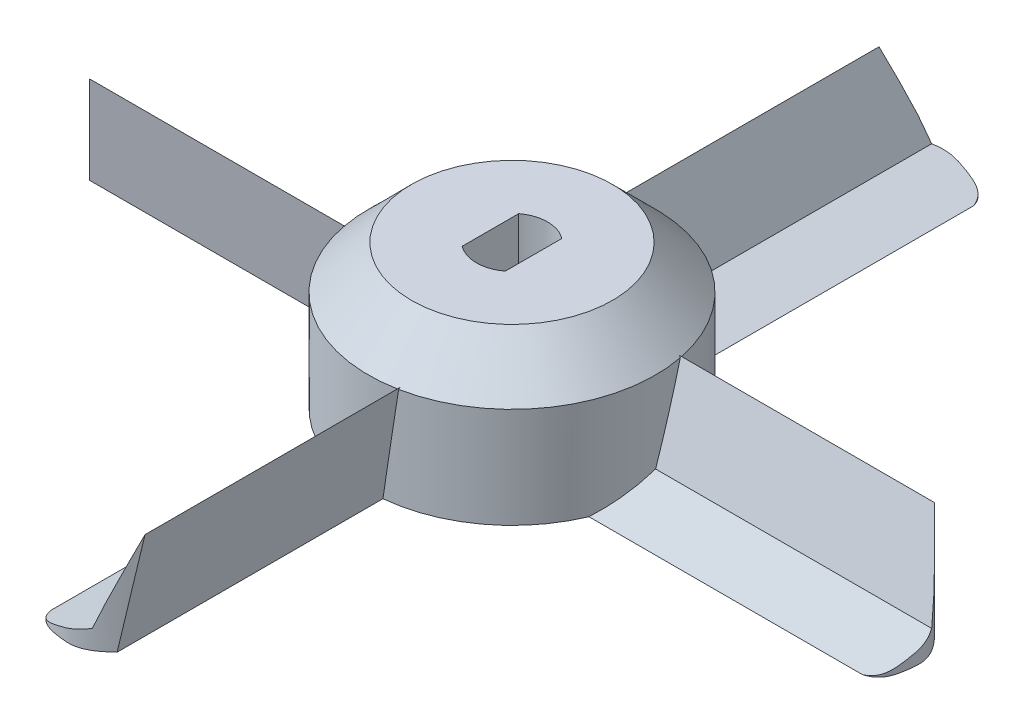
SolidWorks part; units mm, degrees
ref_plane "Front Plane" through (0, 0, 0) normal (0, 0, 1) x (1, 0, 0)
ref_plane "Top Plane" through (0, 0, 0) normal (0, 1, 0) x (1, 0, 0)
ref_plane "Right Plane" through (0, 0, 0) normal (1, 0, 0) x (0, 0, -1)
sketch "Sketch1" plane through (0, 0, 0) normal (0, 1, 0) x (1, 0, 0)
  circle A0 centre (0, 0) radius 10
  dimension "D1" = 20
extrude "Boss-Extrude2" add sketch "Sketch1" along normal blind 10
ref_plane "Plane2" through (0, 0, 8) normal (0, 0, 1) x (1, 0, 0)
ref_plane "Plane3" through (0, 0, 30) normal (0, 0, 1) x (1, 0, 0)
sketch "Sketch2" plane through (0, 0, 8) normal (0, 0, 1) x (1, 0, 0)
  line L0 (0, 11.9193) -> (0, -3.7581) construction
  line L1 (0, 1.3341) -> (1.9332, 7.0864)
  line L2 (1.9332, 7.0864) -> (0.9666, 0)
  line L3 (-10, 0) -> (10, 0) construction
  line L4 (0.9666, 0) -> (-3.8663, 0)
  line L5 (-3.8663, 0) -> (0, 1.3341)
sketch "Sketch3" plane through (0, 0, 30) normal (0, 0, 1) x (1, 0, 0)
  line L0 (0, 1.3341) -> (1.9332, 7.0864)
  line L1 (1.9332, 7.0864) -> (0.9666, 0)
  line L2 (0.9666, 0) -> (-3.8663, 0)
  line L3 (-3.8663, 0) -> (0, 1.3341)
loft "Loft1" add profiles "Sketch2", "Sketch3" connector at (1.9332, 7.0864, 8) connector at (1.9332, 7.0864, 30)
ref_axis "Axis1" through (0, 10, 0) along (0, -1, 0)
pattern_circular "CirPattern1" count 4 over 360 about axis through (0, 10, 0) along (0, -1, 0) of "Loft1"
sketch "Sketch8" plane through (0, 10, 0) normal (0, 1, 0) x (1, 0, 0)
  line L0 (1.5, 1.9687) -> (1.5, -1.9687)
  line L17 (-1.5, 1.9687) -> (-1.5, -1.9687)
  arc A2 (1.5, 1.9687) -> (-1.5, 1.9687) centre (0, 0) ccw
  arc A3 (-1.5, -1.9687) -> (1.5, -1.9687) centre (0, 0) ccw
  point P6 (0, 0)
  point P14 (-1.491, 1.9755)
  dimension "D1" = 4.95
extrude "Cut-Extrude3" cut sketch "Sketch8" against normal blind 6.15 contours L0 A3 L17 A2
sketch "Sketch9" plane through (0, 0, 0) normal (0, -1, 0) x (1, 0, 0)
  line L0 (9.2223, 3.8663) -> (30, 3.8663) construction
  line L1 (9.9532, -0.9666) -> (30, -0.9666) construction
  line L3 (28.2747, 3.8663) -> (30.0234, 3.8663)
  line L4 (30.0234, 3.8663) -> (30.0234, -1.9332)
  line L5 (30.0234, -1.9332) -> (27.4896, -1.9332)
  spline S0 degree 3 poles (28.2747, 3.8663) (29.2516, 3.5799) (29.5037, 2.4698) (29.7813, 0.0895) (28.2575, -1.1531) (27.4896, -1.9332) knots 0 0 0 0 0.329035 0.484269 1 1 1 1
extrude "Cut-Extrude4" cut sketch "Sketch9" against normal blind 8.45
pattern_circular "CirPattern2" count 4 over 360 about axis through (0, 10, 0) along (0, 1, 0) of "Cut-Extrude4"
chamfer "Chamfer1" distance 3 angle 45 1 edges at (0, 10, 10)
